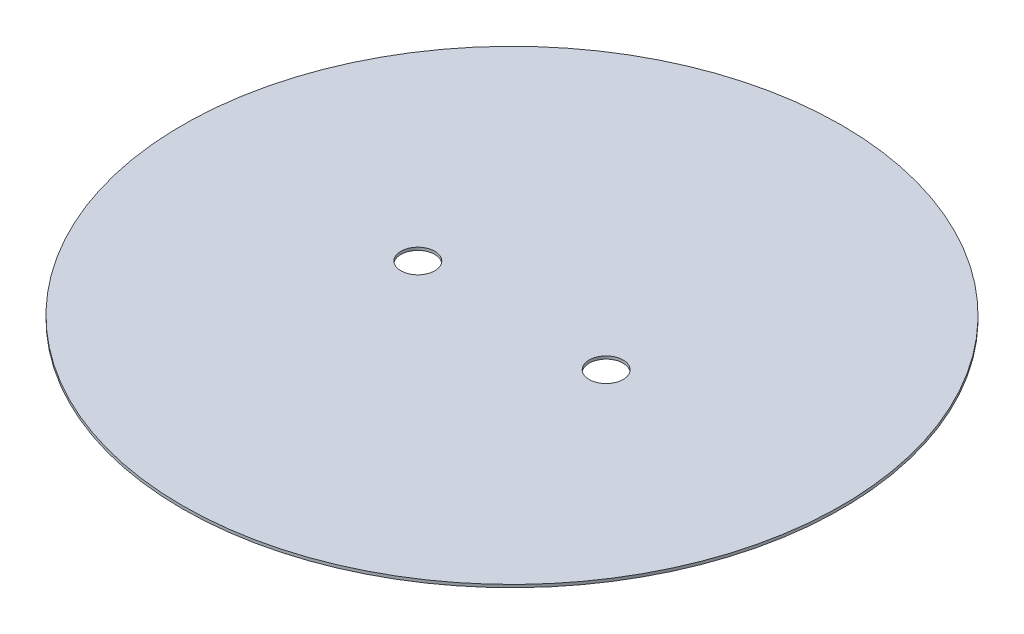
SolidWorks part; units mm, degrees
ref_plane "Front Plane" through (0, 0, 0) normal (0, 0, 1) x (1, 0, 0)
ref_plane "Top Plane" through (0, 0, 0) normal (0, 1, 0) x (1, 0, 0)
ref_plane "Right Plane" through (0, 0, 0) normal (1, 0, 0) x (0, 0, -1)
sketch "Sketch1" plane through (0, 0, 0) normal (0, 1, 0) x (1, 0, 0)
  circle A0 centre (0, 0) radius 1750
extrude "Boss-Extrude1" add sketch "Sketch1" along normal blind 15
sketch "Sketch2" plane through (0, 15, 0) normal (0, 1, 0) x (1, 0, 0)
  line L0 (-8.25, 0) -> (8.25, 0) construction
  line L1 (0, -8.25) -> (0, 8.25) construction
  circle A0 centre (-500, 0) radius 90
  circle A1 centre (500, 0) radius 90
extrude "Cut-Extrude1" cut sketch "Sketch2" against normal blind 50
